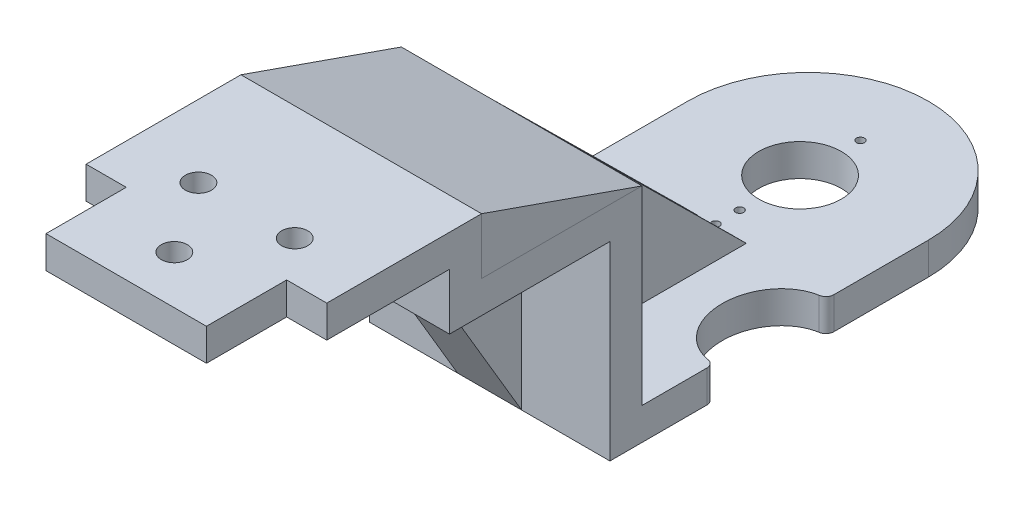
SolidWorks part; units mm, degrees
ref_plane "Спереди" through (0, 0, 0) normal (0, 0, 1) x (1, 0, 0)
ref_plane "Сверху" through (0, 0, 0) normal (0, 1, 0) x (1, 0, 0)
ref_plane "Справа" through (0, 0, 0) normal (1, 0, 0) x (0, 0, -1)
sketch "Эскиз1" plane through (0, 0, 0) normal (0, 1, 0) x (1, 0, 0)
  line L0 (-10, 0) -> (10, 0)
  line L1 (10, 0) -> (10, 10)
  line L2 (10, 10) -> (15, 10)
  line L3 (15, 10) -> (15, 25.3)
  line L4 (15, 25.3) -> (-15, 25.3)
  line L5 (-15, 25.3) -> (-15, 10)
  line L6 (-15, 10) -> (-10, 10)
  line L7 (-10, 10) -> (-10, 0)
  line L8 (0, 0) -> (0, 25.3) construction
  line L9 (-15, 15) -> (15, 15) construction
  circle A0 centre (-6, 15) radius 1.625
  circle A1 centre (0, 6) radius 1.625
  circle A2 centre (6, 15) radius 1.625
  dimension "D6" = 3.25
  dimension "D1" = 20
  dimension "D2" = 10
  dimension "D3" = 5
  dimension "D4" = 15.3
  dimension "D5" = 5
  dimension "D7" = 9
  dimension "D8" = 6
extrude "Бобышка-Вытянуть1" add sketch "Эскиз1" along normal blind 4
sketch "Эскиз2" plane through (0, 0, -25.3) normal (0, 0, -1) x (-1, 0, 0)
  line L0 (-15, 4) -> (15, 4)
  line L1 (-15, 4) -> (-15, -7)
  line L2 (15, 4) -> (15, -7)
  line L3 (-15, -7) -> (15, -7)
  line L4 (-15, 0) -> (15, 0) construction
  dimension "D1" = 7
extrude "Бобышка-Вытянуть2" add sketch "Эскиз2" along normal blind 4
sketch "Эскиз3" plane through (0, -7, 0) normal (0, -1, 0) x (1, 0, 0)
  line L0 (-15, -25.3) -> (15, -25.3)
  line L1 (-15, -25.3) -> (-15, -49.3)
  line L2 (15, -25.3) -> (15, -49.3)
  line L3 (-15, -49.3) -> (15, -49.3)
  dimension "D1" = 24
extrude "Бобышка-Вытянуть3" add sketch "Эскиз3" against normal blind 4
sketch "Эскиз4" plane through (-15, 0, 0) normal (-1, 0, 0) x (0, 0, 1)
  line L0 (-29.3, 4) -> (-29.3, -3)
  line L1 (-29.3, -3) -> (-49.3, -3)
  line L2 (-29.3, -3) -> (-49.3, -3) construction
  line L3 (-49.3, -3) -> (-29.3, 4)
  dimension "D1" = 20
extrude "Бобышка-Вытянуть4" add sketch "Эскиз4" against normal through all
sketch "Эскиз5" plane through (15, 0, 0) normal (1, 0, 0) x (0, 0, -1)
  line L0 (49.3, -7) -> (25.3, -7) construction
  line L1 (49.3, -7) -> (45.3, -7)
  line L2 (49.3, -7) -> (49.3, -30.7)
  line L3 (49.3, -30.7) -> (45.3, -30.7)
  line L4 (45.3, -7) -> (45.3, -30.7)
  line L5 (25.3, 0) -> (25.3, -7) construction
  dimension "D1" = 4
  dimension "D2" = 23.7
  dimension "D3" = 24
extrude "Бобышка-Вытянуть5" add sketch "Эскиз5" against normal through all
sketch "Эскиз6" plane through (0, -30.7, 0) normal (0, -1, 0) x (1, 0, 0)
  line L0 (-15.0001, -45.3) -> (15, -45.3)
  line L1 (-15.0001, -45.3) -> (-15.0001, -100)
  line L2 (15, -45.3) -> (15, -100)
  line L3 (-15.0001, -100) -> (15, -100)
  line L4 (-15.0001, -84) -> (15, -84) construction
  line L5 (0, -100) -> (0, -45.3) construction
  circle A0 centre (0, -84) radius 5.15
  dimension "D3" = 10.3
  dimension "D1" = 54.7
  dimension "D2" = 16
extrude "Бобышка-Вытянуть6" add sketch "Эскиз6" against normal blind 4
sketch "Эскиз7" [suppressed] plane through (-15, 0, 0) normal (-1, 0, 0) x (0, 0, 1)
  line L0 (-45.3, -7) -> (-45.3, -17)
  line L1 (-45.3, -7) -> (-45.3, -17) construction
  line L2 (-45.3, -17) -> (-25.3, -7)
  line L3 (-25.3, -7) -> (-45.3, -7)
  line L4 (-49.3, -17) -> (-49.3, -3)
  line L5 (-49.3, -3) -> (-69.3, -17)
  line L6 (-45.3, -17) -> (-100, -17) construction
  line L7 (-69.3, -17) -> (-49.3, -17)
  dimension "D1" = 20
  dimension "D2" = 10
  dimension "D3" = 20
extrude "Бобышка-Вытянуть7" [suppressed] add sketch "Эскиз7" against normal through all
sketch "Эскиз8" plane through (0, -30.7, 0) normal (0, -1, 0) x (1, 0, 0)
  line L0 (0, -100) -> (0, -45.3) construction
  line L1 (-15.0001, -100) -> (15, -100) construction
  line L2 (-15, -45.3) -> (15, -45.3) construction
  line L3 (15, -45.3) -> (15, -100) construction
  ellipse E0 centre (15, -65.3) end of major axis (15, -72.3) minor radius 6
  ellipse E1 centre (-15, -65.3) end of major axis (-15, -72.3) minor radius 6
  dimension "D1" = 20
extrude "Вырез-Вытянуть1" cut sketch "Эскиз8" against normal up to next
fillet "Скругление2" radius 1 4 edges at (15, -28.7, -72.3) (-15.0001, -28.7, -58.3) (15, -28.7, -58.3)
fillet "Скругление3" radius 15 2 edges at (-15.0001, -28.7, -100) (15, -28.7, -100)
ref_plane "Плоскость1" through (0, 0, 0) normal (-1, 0, 0) x (0, 0, 1)
sketch "Эскиз10" plane through (0, 0, 0) normal (-1, 0, 0) x (0, 0, 1)
  line L0 (-49.3, -26.7) -> (-73.3, -26.7)
  line L1 (-85, -26.7) -> (-73.2182, -26.7) construction
  line L2 (-73.3, -26.7) -> (-49.3, -3)
  line L3 (-49.3, -3) -> (-49.3, -26.7) construction
  line L4 (-49.3, -3) -> (-49.3, -26.7)
  dimension "D1" = 24
extrude "Бобышка-Вытянуть8" add sketch "Эскиз10" along normal blind 4 and the other way blind 4
sketch "Эскиз11" plane through (0, 0, 0) normal (-1, 0, 0) x (0, 0, 1)
  line L0 (-31.3, -7) -> (-45.3, -7)
  line L1 (-45.3, -7) -> (-45.3, -30.7)
  line L2 (-45.3, -7) -> (-45.3, -30.7) construction
  line L3 (-45.3, -30.7) -> (-31.3, -7)
  line L4 (-45.3, -7) -> (-25.3, -7) construction
  dimension "D1" = 14
extrude "Бобышка-Вытянуть9" add sketch "Эскиз11" along normal blind 4 and the other way blind 4
ref_point "Точка1"
sketch "Эскиз13" plane through (0, -30.7, 0) normal (0, -1, 0) x (1, 0, 0)
  line L0 (0, -100) -> (0, -45.3) construction
  line L1 (4, -45.3) -> (-4, -45.3) construction
  arc A0 (0, -100) -> (15, -85) centre (0, -85) ccw construction
  circle A1 centre (0, -76.47) radius 0.5
  circle A2 centre (0, -73.47) radius 0.5
  circle A3 centre (0, -70.47) radius 0.5
  circle A4 centre (0, -67.47) radius 0.5
  circle A5 centre (0, -91.53) radius 0.5
  point P17 (0, -84)
  dimension "D1" = 1
  dimension "D2" = 7.53
  dimension "D3" = 7.53
  dimension "D4" = 10.53
  dimension "D5" = 13.53
  dimension "D6" = 16.53
extrude "Вырез-Вытянуть2" cut sketch "Эскиз13" against normal blind 20
sketch "Эскиз14" plane through (0, -26.7, 0) normal (0, 1, 0) x (1, 0, 0)
  line L0 (-0.4702, 73.3) -> (-4, 73.3) construction
  line L1 (-2, 73.3) -> (2, 73.3)
  line L2 (-2, 73.3) -> (-2, 65.3)
  line L3 (-2, 65.3) -> (2, 65.3)
  line L4 (2, 73.3) -> (2, 65.3)
  line L6 (-4, 49.3) -> (-4, 73.3) construction
  line L7 (4, 73.3) -> (4, 49.3) construction
  dimension "D1" = 2
  dimension "D2" = 2
  dimension "D3" = 4
  dimension "D4" = 8
extrude "Вырез-Вытянуть3" cut sketch "Эскиз14" along normal blind 10
